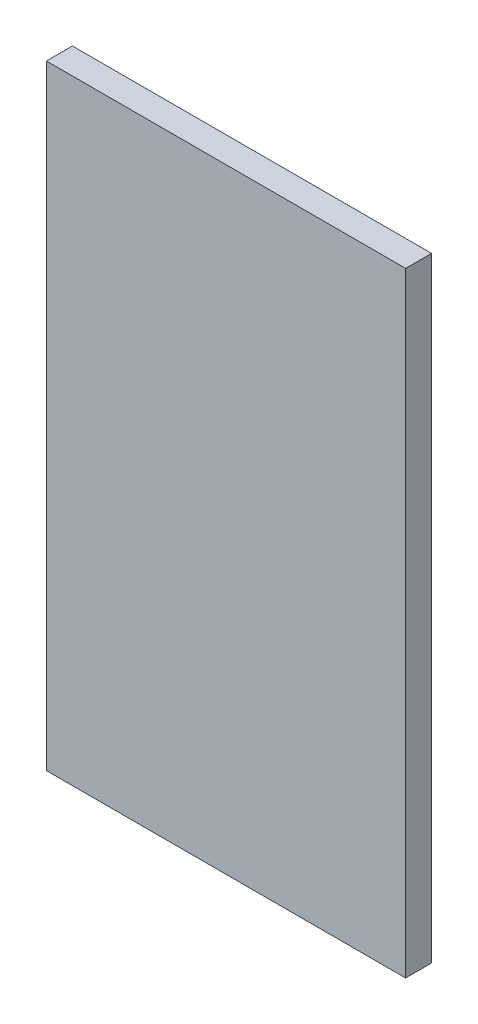
SolidWorks part; units mm, degrees
material "Pine"
ref_plane "Front Plane" through (0, 0, 0) normal (0, 0, 1) x (1, 0, 0)
ref_plane "Top Plane" through (0, 0, 0) normal (0, 1, 0) x (1, 0, 0)
ref_plane "Right Plane" through (0, 0, 0) normal (1, 0, 0) x (0, 0, -1)
sketch "Sketch3" plane through (0, 0, 0) normal (0, 0, 1) x (1, 0, 0)
  line L4 (417, 214) -> (583, 214)
  line L5 (417, 214) -> (417, -70)
  line L6 (417, -70) -> (583, -70)
  line L7 (583, 214) -> (583, -70)
  line L8 (417, 214) -> (583, -70) construction
  line L9 (417, -70) -> (583, 214) construction
  point P6 (500, 72)
  dimension "D1" = 166
  dimension "D2" = 284
extrude "Boss-Extrude2" add sketch "Sketch3" along normal blind 12 separate body
sketch "Sketch4" [suppressed] plane through (0, 0, 12) normal (0, 0, 1) x (1, 0, 0)
  line L1 (442.6085, 191.5854) -> (556.8131, 191.5854)
  line L2 (432.6085, 181.5854) -> (432.6085, 99.4004)
  line L3 (442.6085, 89.4004) -> (556.8131, 89.4004)
  line L4 (566.8131, 181.5854) -> (566.8131, 99.4004)
  line L5 (432.6085, 191.5854) -> (566.8131, 89.4004) construction
  line L6 (432.6085, 89.4004) -> (566.8131, 191.5854) construction
  line L7 (438.5839, 77.616) -> (560.5839, 77.616) construction
  line L8 (438.5839, 77.616) -> (438.5839, -46.384) construction
  line L9 (438.5839, -46.384) -> (560.5839, -46.384) construction
  line L10 (560.5839, 77.616) -> (560.5839, -46.384) construction
  line L11 (213.067, 66.7937) -> (345.067, 66.7937) construction
  line L12 (213.067, 66.7937) -> (213.067, -0.2063) construction
  line L13 (213.067, -0.2063) -> (345.067, -0.2063) construction
  line L14 (345.067, 66.7937) -> (345.067, -0.2063) construction
  line L15 (465.4441, 183.8582) -> (567.4441, 183.8582)
  line L16 (465.4441, 183.8582) -> (465.4441, 98.8582)
  line L17 (465.4441, 98.8582) -> (567.4441, 98.8582)
  line L18 (567.4441, 183.8582) -> (567.4441, 98.8582)
  arc A0 (432.6085, 99.4004) -> (442.6085, 89.4004) centre (442.6085, 99.4004) ccw
  arc A1 (556.8131, 89.4004) -> (566.8131, 99.4004) centre (556.8131, 99.4004) ccw
  arc A2 (556.8131, 191.5854) -> (566.8131, 181.5854) centre (556.8131, 181.5854) cw
  arc A3 (442.6085, 191.5854) -> (432.6085, 181.5854) centre (442.6085, 181.5854) ccw
  point P0 (499.7108, 140.4929)
  dimension "D1" = 10
equation "\"LENGTH\" = 1000mm"
equation "\"PLY\"= 12mm"
equation "\"CENTER_BRACE_LENGTH\" = 393mm"
equation "\"PANEL_WIDTH\"= \"LENGTH\" - \"CENTER_BRACE_LENGTH\" * 2 - \"PLY\" * 4"
equation "\"D1@Boss-Extrude2\"=\"PLY\""
equation "\"D1@Sketch3\"=\"PANEL_WIDTH\""
equation "\"PANEL_SMALL_HEIGHT\" = 70mm"
equation "\"D2@Sketch3\"=\"WIDTH\" - \"PLY\" * 2 + \"HOUSING_DEPTH\" * 2"
equation "\"WIDTH\" = 300mm"
equation "\"HEIGHT\" = 300mm"
equation "\"HOUSING_DEPTH\" = 4mm"
equation "\"PORT_WIDTH\" = 90mm"
equation "\"PORT_RADIUS\" = 15mm"
equation "\"PORT_BRACE_HEIGHT\" = 92mm"
equation "\"DOWEL_SIZE\" = 0.25in"
equation "\"DOWEL_OFFSET\" = 30mm"
